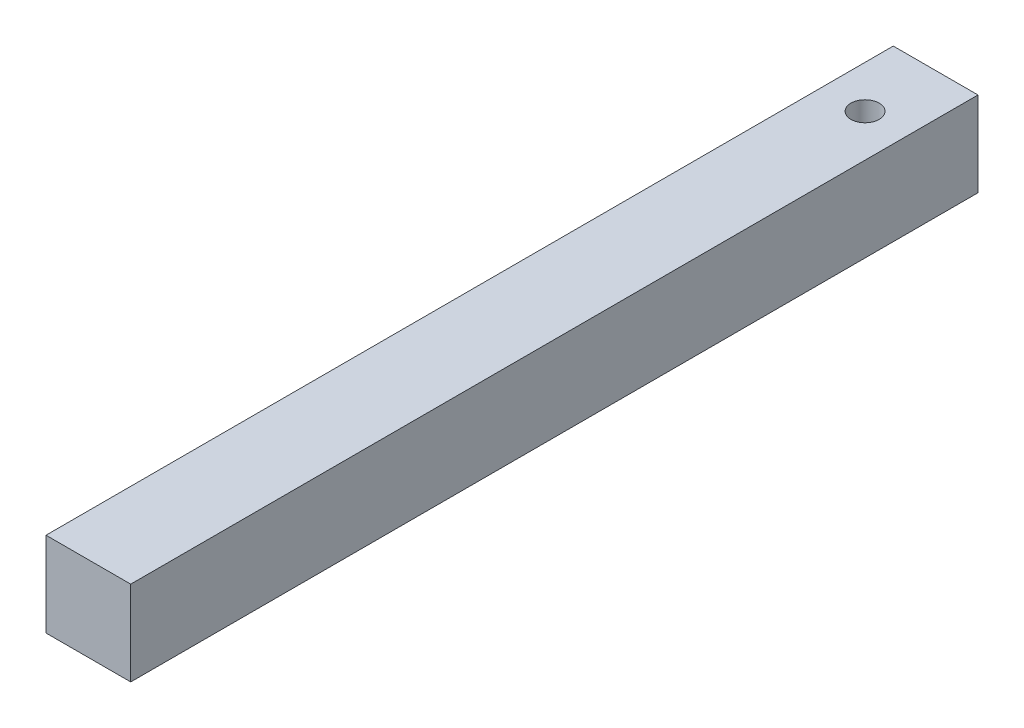
SolidWorks part; units mm, degrees
other "Leg"
material "ASTM A36 Steel"
ref_plane "Front Plane" through (0, 0, 0) normal (0, 0, 1) x (1, 0, 0)
ref_plane "Top Plane" through (0, 0, 0) normal (0, 1, 0) x (1, 0, 0)
ref_plane "Right Plane" through (0, 0, 0) normal (1, 0, 0) x (0, 0, -1)
sketch "Sketch1" plane through (0, 0, 0) normal (0, 1, 0) x (1, 0, 0)
  line L13 (-9.525, 95.25) -> (9.525, 95.25)
  line L14 (-9.525, 95.25) -> (-9.525, -95.25)
  line L15 (-9.525, -95.25) -> (9.525, -95.25)
  line L16 (9.525, 95.25) -> (9.525, -95.25)
  line L17 (-9.525, 95.25) -> (9.525, -95.25) construction
  line L18 (-9.525, -95.25) -> (9.525, 95.25) construction
  point P0 (0, 0)
  dimension "D1" = 19.05
  dimension "D2" = 190.5
extrude "Profile" add sketch "Sketch1" along normal blind 19.05
sketch "Sketch2" plane through (0, 19.05, 0) normal (0, 1, 0) x (1, 0, 0)
  line L0 (9.525, 95.25) -> (-9.525, 84.2515)
  line L1 (9.525, 95.25) -> (-9.525, 95.25) construction
  line L3 (-9.525, 95.25) -> (-9.525, -95.25) construction
  line M3 (9.525, 95.25) -> (-9.525, 95.25)
  line M4 (-9.525, 95.25) -> (-9.525, -95.25)
  dimension "D1" = 30
extrude "30deg Top Cut" [suppressed] cut sketch "Sketch2" against normal blind 25.654 and the other way through all contours L0 M3 M4
sketch "Sketch3" [suppressed] plane through (-39.5506, 0, -68.5037) normal (-0.5, 0, -0.866) x (-0.866, 0, 0.5)
  line L0 (-34.6706, 9.525) -> (-56.6676, 9.525) construction
  line L1 (-34.6706, 19.05) -> (-34.6706, 0) construction
  line L2 (-56.6676, 19.05) -> (-56.6676, 0) construction
  point P6 (-45.6691, 9.525)
sketch "Sketch4" plane through (0, 19.05, 0) normal (0, 1, 0) x (1, 0, 0)
  line L0 (9.525, -95.25) -> (-9.525, -84.2515)
  line L3 (-9.525, 95.25) -> (-9.525, -95.25) construction
  line L4 (-9.525, -95.25) -> (9.525, -95.25) construction
  point P7 (0, 0)
  dimension "D1" = 30
extrude "30deg Bottom Cut" [suppressed] cut sketch "Sketch4" against normal blind 44.704 and the other way through all
sketch "Sketch8" [suppressed] plane through (0, 19.05, 0) normal (0, 1, 0) x (1, 0, 0)
  line L0 (0, 91.3382) -> (0, 75.4632) construction
  circle A0 centre (0, 75.4632) radius 1.5
  dimension "D1" = 3
  dimension "D2" = 15.875
extrude "Adapter Hole" [suppressed] cut sketch "Sketch8" against normal blind 30.988
sketch "Sketch9" plane through (0, 0, -95.25) normal (0, 0, -1) x (-1, 0, 0)
  line L0 (0, 0) -> (0, 19.05) construction
  line L1 (-9.525, 19.05) -> (9.525, 19.05) construction
  point P5 (0, 9.525)
sketch "Sketch10" plane through (0, 19.05, 0) normal (0, 1, 0) x (1, 0, 0)
  line L0 (0, 95.25) -> (0, 79.375) construction
  circle A0 centre (0, 79.375) radius 3.175
  dimension "D1" = 6.35
  dimension "D2" = 15.875
extrude "Cut-Extrude1" cut sketch "Sketch10" against normal blind 41.148
